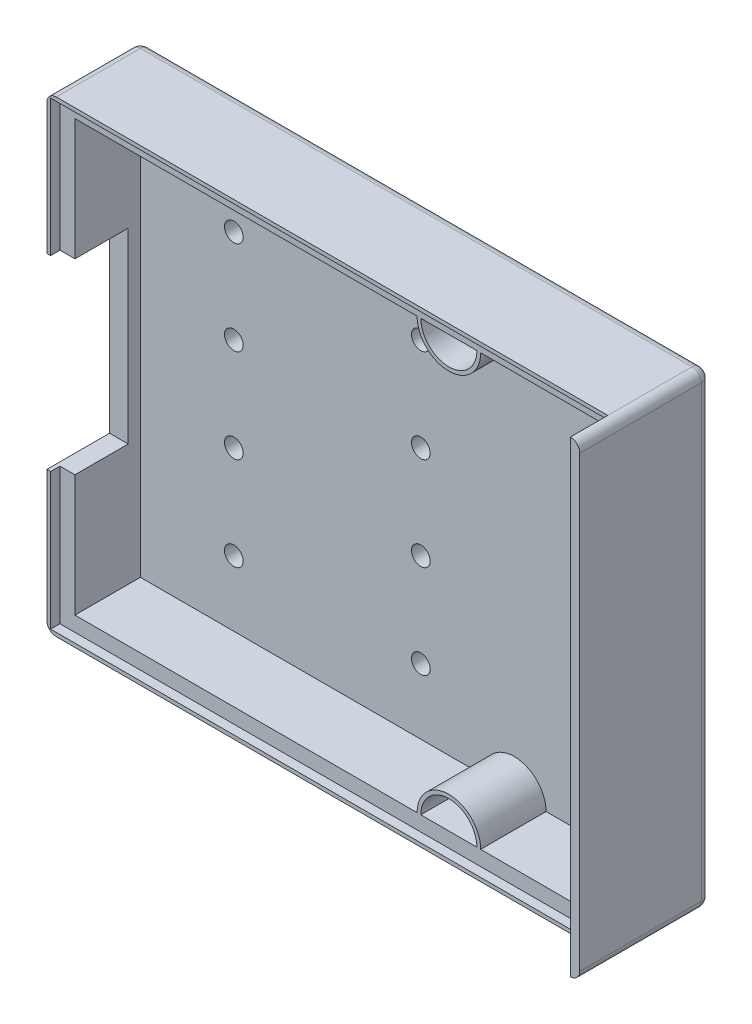
SolidWorks part; units mm, degrees
material "Plastique personnalisé"
ref_plane "Plan de face" through (0, 0, 0) normal (0, 0, 1) x (1, 0, 0)
ref_plane "Plan de dessus" through (0, 0, 0) normal (0, 1, 0) x (1, 0, 0)
ref_plane "Plan de droite" through (0, 0, 0) normal (1, 0, 0) x (0, 0, -1)
sketch "Esquisse1" plane through (0, 0, 0) normal (0, 0, 1) x (1, 0, 0)
  line L1 (0, 0) -> (30, 0)
  line L2 (0, 0) -> (0, 25)
  line L3 (0, 25) -> (30, 25)
  line L4 (30, 0) -> (30, 25)
  line L5 (0, 0) -> (30, 25) construction
  line L6 (0, 25) -> (30, 0) construction
  point P4 (15, 12.5)
  dimension "D1" = 25
  dimension "D2" = 30
extrude "Boss.-Extru.1" add sketch "Esquisse1" along normal blind 5
sketch "Esquisse2" plane through (0, 0, 5) normal (0, 0, 1) x (1, 0, 0)
  line L0 (1, 24) -> (1, 1)
  line L1 (1, 1) -> (29, 1)
  line L2 (29, 1) -> (29, 24)
  line L3 (29, 24) -> (1, 24)
  line L4 (0, 25) -> (0, 0)
  line L5 (0, 0) -> (30, 0)
  line L6 (30, 0) -> (30, 25)
  line L7 (30, 25) -> (0, 25)
  line L8 (0, 25) -> (0, 0)
  line L9 (0, 0) -> (30, 0)
  line L10 (30, 0) -> (30, 25)
  line L11 (30, 25) -> (0, 25)
  dimension "D1" = 0
  dimension "D2" = 1
extrude "Enlèv. mat.-Extru.1" cut sketch "Esquisse2" against normal blind 4 contours L2 L3 L0 L1 region at (15, 12.5, 5)
sketch "Esquisse3" plane through (0, 0, 0) normal (-1, 0, 0) x (0, 0, 1)
  line L0 (5, 17.5) -> (1.65, 17.5)
  line L3 (1.65, 17.5) -> (1.65, 7.5)
  line L4 (1.65, 7.5) -> (5, 7.5)
  line L6 (5, 7.5) -> (5, 17.5)
  line L7 (5, 25) -> (5, 0) construction
  line L8 (5, 0) -> (0, 0) construction
  line L9 (5, 25) -> (0, 25) construction
  line L10 (0, 25) -> (0, 0) construction
  dimension "D1" = 7.5
  dimension "D2" = 7.5
  dimension "D3" = 1.65
extrude "Enlèv. mat.-Extru.2" cut sketch "Esquisse3" against normal blind 10
sketch "Esquisse4" plane through (30, 0, 0) normal (1, 0, 0) x (0, 0, -1)
  line L0 (-5, 1) -> (-1, 1)
  line L1 (-5, 0) -> (-5, 25) construction
  line L2 (-1, 1) -> (-1, 24)
  line L3 (-1, 24) -> (-5, 24)
  line L4 (-5, 24) -> (-5, 1)
  line L5 (-5, 25) -> (0, 25) construction
  line L6 (-5, 0) -> (0, 0) construction
  line L7 (0, 0) -> (0, 25) construction
  dimension "D1" = 1
  dimension "D2" = 1
  dimension "D3" = 1
extrude "Enlèv. mat.-Extru.3" cut sketch "Esquisse4" against normal blind 10
sketch "Esquisse5" plane through (0, 0, 1) normal (0, 0, 1) x (1, 0, 0)
  line L0 (19.5, 1) -> (22.5, 1)
  line L1 (19.5, 24) -> (22.5, 24)
  line L2 (19.3118, 24.2) -> (22.6882, 24.2)
  line L3 (19.3118, 0.8) -> (22.6882, 0.8)
  line L4 (30, 1) -> (30, 24) construction
  line L5 (30, 24) -> (1, 24) construction
  line L6 (1, 1) -> (30, 1) construction
  arc A0 (22.5, 1) -> (19.5, 1) centre (21, 1) ccw
  arc A2 (19.5, 24) -> (22.5, 24) centre (21, 24) ccw
  arc A3 (19.3118, 24.2) -> (22.6882, 24.2) centre (21, 24) ccw
  arc A4 (22.6882, 0.8) -> (19.3118, 0.8) centre (21, 1) ccw
  dimension "D1" = 1.5
  dimension "D2" = 1.5
  dimension "D3" = 9
  dimension "D4" = 9
  dimension "D5" = 0.2
  dimension "D6" = 0.2
extrude "Boss.-Extru.2" add sketch "Esquisse5" along normal blind 3.5
fillet "Congé3" radius 0.5 5 edges at (0, 0, 2.5) (0, 25, 2.5) (0, 12.5, 0) (15, 25, 0) (15, 0, 0)
sketch "Esquisse9" plane through (0, 0, 5) normal (0, 0, 1) x (1, 0, 0)
  line L0 (0.2, 7.5) -> (0.2, 0.2)
  line L1 (1, 7.5) -> (0, 7.5) construction
  line L2 (0.2, 0.2) -> (30, 0.2)
  line L3 (30, 0) -> (30, 1) construction
  line L4 (30, 0.2) -> (30, 1)
  line L5 (30, 1) -> (1, 1)
  line L6 (1, 1) -> (1, 7.5)
  line L7 (1, 7.5) -> (0.2, 7.5)
  line L8 (0, 7.5) -> (0, 0.5) construction
  line L9 (0.5, 0) -> (30, 0) construction
  line L10 (-0.8724, 12.5) -> (1.7986, 12.5) construction
  line L11 (1, 17.5) -> (0.2, 17.5)
  line L12 (1, 24) -> (1, 17.5)
  line L13 (30, 24) -> (1, 24)
  line L14 (30, 24.8) -> (30, 24)
  line L15 (0.2, 24.8) -> (30, 24.8)
  line L16 (0.2, 17.5) -> (0.2, 24.8)
  dimension "D1" = 0.2
  dimension "D2" = 0.2
  dimension "D3" = 5
extrude "Enlèv. mat.-Extru.6" cut sketch "Esquisse9" against normal blind 0.5
sketch "Esquisse12" plane through (30, 0, 0) normal (1, 0, 0) x (0, 0, -1)
  line L1 (0, 0) -> (-7, 0)
  line L2 (0, 0) -> (0, 25)
  line L3 (0, 25) -> (-7, 25)
  line L4 (-7, 0) -> (-7, 25)
  line L5 (0, 0) -> (-7, 25) construction
  line L6 (0, 25) -> (-7, 0) construction
  point P4 (-3.5, 12.5)
  dimension "D1" = 7
  dimension "D2" = 25
extrude "Boss.-Extru.5" add sketch "Esquisse12" along normal blind 0.5
fillet "Congé5" radius 0.5 3 edges at (30.5, 0, 3.5) (30.5, 25, 3.5) (30.5, 12.5, 0)
sketch "Esquisse13" plane through (0, 0, 0) normal (0, 0, -1) x (-1, 0, 0)
  line L0 (-30, 24.5) -> (-30, 0.5) construction
  line L1 (-0.5, 24.5) -> (-30, 24.5) construction
  circle A0 centre (-26, 19.5) radius 0.5
  circle A1 centre (-16, 19.5) radius 0.5
  circle A2 centre (-6, 19.5) radius 0.5
  circle A3 centre (-16, 14.5) radius 0.5
  circle A4 centre (-6, 14.5) radius 0.5
  circle A5 centre (-16, 9.5) radius 0.5
  circle A6 centre (-6, 9.5) radius 0.5
  circle A7 centre (-16, 4.5) radius 0.5
  circle A8 centre (-6, 4.5) radius 0.5
  circle A9 centre (-26, 14.5) radius 0.5
  circle A10 centre (-26, 9.5) radius 0.5
  circle A11 centre (-26, 4.5) radius 0.5
  dimension "D5" = 1
  dimension "D3" = 4
  dimension "D4" = 5
  dimension "D1" = 3
  dimension "D2" = 4
extrude "Enlèv. mat.-Extru.8" cut sketch "Esquisse13" against normal blind 10.5
